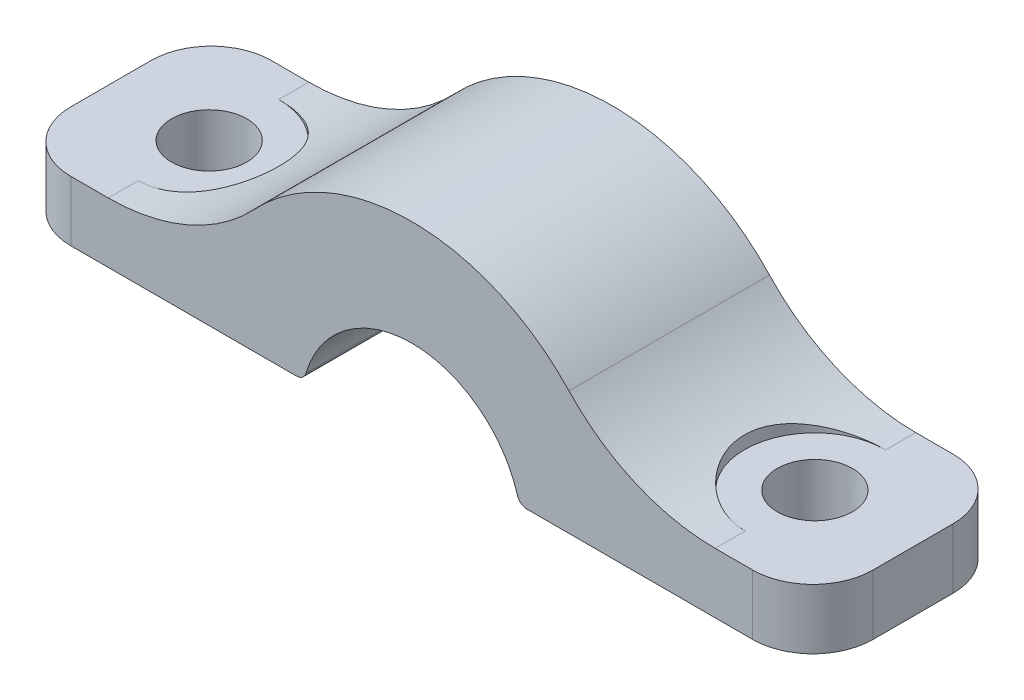
SolidWorks part; units mm, degrees
ref_plane "Front Plane" through (0, 0, 0) normal (0, 0, 1) x (1, 0, 0)
ref_plane "Top Plane" through (0, 0, 0) normal (0, 1, 0) x (1, 0, 0)
ref_plane "Right Plane" through (0, 0, 0) normal (1, 0, 0) x (0, 0, -1)
sketch "Sketch1" plane through (0, 0, 0) normal (0, 1, 0) x (1, 0, 0)
  line L1 (-20, 5) -> (20, 5)
  line L2 (-20, 5) -> (-20, -5)
  line L3 (-20, -5) -> (20, -5)
  line L4 (20, 5) -> (20, -5)
  line L5 (-20, 5) -> (20, -5) construction
  line L6 (-20, -5) -> (20, 5) construction
  point P0 (0, 0)
  dimension "D1" = 40
  dimension "D2" = 10
sketch "Sketch2" plane through (0, 0, 0) normal (0, 0, 1) x (1, 0, 0)
  line L0 (-4.7339, 0) -> (4.7339, 0) construction
  line L1 (0, -55) -> (0, 55) construction
  line L2 (-10.3789, 0) -> (10.3789, 0) construction
  line L3 (-10.3789, 0) -> (-4.7339, 0)
  line L4 (4.7339, 0) -> (10.3789, 0)
  arc A0 (-4.7339, 0) -> (4.7339, 0) centre (0, 2.8) cw
  arc A2 (-10.3789, 0) -> (10.3789, 0) centre (0, 2.8) cw
  point P3 (0, 2.8)
  point P4 (0, 0)
  point P5 (-4.7339, 0)
  point P6 (4.7339, 0)
  dimension "D4" = 10.75
  dimension "D1" = 2.8
  dimension "D2" = 5.5
  dimension "D3" = 5.5
extrude "Boss-Extrude1" add sketch "Sketch1" against normal blind 5 from offset 1 offset against normal yes
extrude "Boss-Extrude2" add sketch "Sketch2" along normal blind 5 and the other way blind 5
sketch "Sketch3" plane through (0, 0, 0) normal (0, 1, 0) x (1, 0, 0)
  line L0 (-10.75, -5) -> (10.75, -5) construction
  line L1 (-20, 5) -> (-8, 5)
  line L2 (-20, 5) -> (-20, -5)
  line L3 (-20, -5) -> (-8, -5)
  line L4 (-8, 5) -> (-8, -5)
  line L5 (0, -5.5) -> (0, 5.5) construction
  line L6 (20, -5) -> (8, -5)
  line L7 (20, 5) -> (20, -5)
  line L8 (20, 5) -> (8, 5)
  line L9 (8, 5) -> (8, -5)
  dimension "D1" = 12
extrude "Boss-Extrude3" add sketch "Sketch3" along normal blind 7
fillet "Fillet1" radius 3 4 edges at (20, 3.5, -5) (20, 3.5, 5) (-20, 3.5, -5) (-20, 3.5, 5)
fillet "Fillet2" radius 3 4 edges at (-20, -3.5, 5) (-20, -3.5, -5) (20, -3.5, 5) (20, -3.5, -5)
fillet "Fillet4" radius 10 2 edges at (9.8956, 7, 0) (-9.8956, 7, 0)
sketch "Sketch4" plane through (0, 0, 0) normal (0, 1, 0) x (1, 0, 0)
  line L0 (-10.7525, 0) -> (10.7525, 0) construction
  circle A0 centre (-15.1, 0) radius 1.875
  circle A1 centre (15.1, 0) radius 1.875
  dimension "D1" = 3.75
  dimension "D2" = 15.1
  dimension "D3" = 15.1
extrude "Cut-Extrude1" cut sketch "Sketch4" against normal through all both and the other way through all
sketch "Sketch5" plane through (0, 0, 0) normal (0, 1, 0) x (1, 0, 0)
  line L0 (0, -5.5) -> (0, 5.5) construction
  circle A0 centre (-15.1, 0) radius 3.5
  circle A1 centre (15.1, 0) radius 3.5
  dimension "D1" = 7
extrude "Cut-Extrude2" cut sketch "Sketch5" along normal blind 10 from offset 7
sketch "Sketch9" plane through (0, 0, 0) normal (0, 1, 0) x (1, 0, 0)
  line L1 (25.6287, -11.6641) -> (-21.4657, -11.6641)
  line L2 (25.6287, -11.6641) -> (25.6287, 11.6724)
  line L3 (25.6287, 11.6724) -> (-21.4657, 11.6724)
  line L4 (-21.4657, -11.6641) -> (-21.4657, 11.6724)
extrude "Cut-Extrude5" cut sketch "Sketch9" along normal blind 4
fillet "Fillet5" radius 0.5 2 edges at (-5.3675, 4, 0) (5.3675, 4, 0)
sketch "Sketch7" plane through (0, 0, 0) normal (0, 1, 0) x (1, 0, 0)
  line L5 (24.1582, -13.2438) -> (-27.5449, -13.2438)
  line L6 (24.1582, -13.2438) -> (24.1582, 9.8009)
  line L7 (24.1582, 9.8009) -> (-27.5449, 9.8009)
  line L8 (-27.5449, -13.2438) -> (-27.5449, 9.8009)
extrude "Cut-Extrude4" cut sketch "Sketch7" against normal through all
equation "\"shaftDiameter\"= 10mm"
equation "\"holeDiameter\"= 3.75mm"
equation "\"D1@Sketch4\"=\"holeDiameter\""
